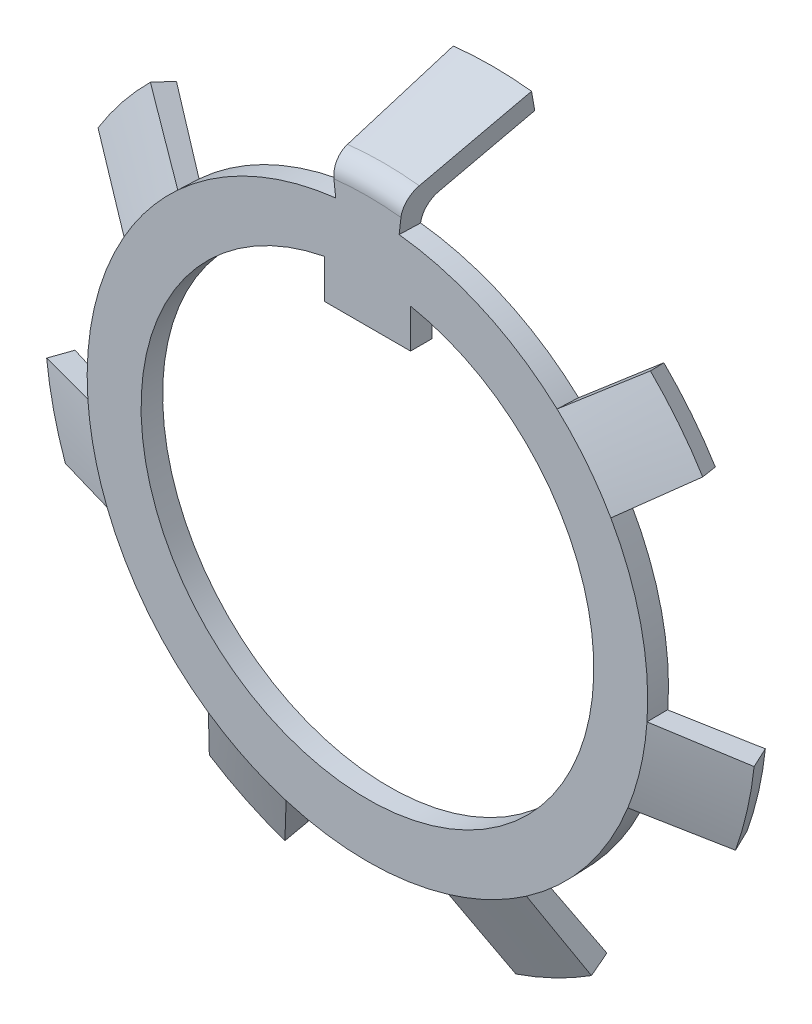
SolidWorks part; units mm, degrees
ref_plane "Front Plane" through (0, 0, 0) normal (0, 0, 1) x (1, 0, 0)
ref_plane "Top Plane" through (0, 0, 0) normal (0, 1, 0) x (1, 0, 0)
ref_plane "Right Plane" through (0, 0, 0) normal (1, 0, 0) x (0, 0, -1)
sketch "Sketch1" plane through (0, 0, 0) normal (1, 0, 0) x (0, 0, -1)
  line L0 (-1, 0) -> (23.0727, 0) construction
  line L1 (-1, 7.5) -> (-1, 13)
  line L2 (-1, 13) -> (0.529, 16.5)
  line L3 (0.529, 16.5) -> (1.4454, 16.0997)
  line L4 (1.4454, 16.0997) -> (0, 13)
  line L5 (0, 13) -> (0, 7.5)
  line L6 (0, 7.5) -> (-1, 7.5)
  dimension "D1" = 15
  dimension "D2" = 1
  dimension "D3" = 25
  dimension "D4" = 33
  dimension "D5" = 26
revolve "Revolve1" add sketch "Sketch1" angle 360 about L0
sketch "Sketch2" plane through (0, 0, 0) normal (0, 0, 1) x (1, 0, 0)
  line L0 (-2, 8.5) -> (-2, 10.3078)
  line L1 (-2, 8.5) -> (2, 8.5)
  line L5 (2, 8.5) -> (2, 10.3078)
  arc A0 (-2, 10.3078) -> (2, 10.3078) centre (0, 0) ccw
  point P1 (0, 8.5)
  dimension "D2" = 4
  dimension "D3" = 10.5
  dimension "D1" = 8.5
extrude "Cut-Extrude2" cut sketch "Sketch2" against normal through all both and the other way through all
sketch "Sketch3" plane through (0, 0, 1) normal (0, 0, 1) x (1, 0, 0)
  line L0 (0, 16.5) -> (0, 13) construction
  line L1 (14.0521, 8.6481) -> (11.2898, 6.4452)
  line L2 (2, 16.3783) -> (2, 12.8452)
  line L3 (-2, 16.3783) -> (-2, 12.8452)
  line L6 (11.5581, 11.7754) -> (8.7958, 9.5725)
  line L7 (15.5227, -5.5944) -> (12.0781, -4.8082)
  line L8 (16.4127, -1.6947) -> (12.9682, -0.9085)
  line L9 (5.3044, -15.6241) -> (3.7714, -12.4409)
  line L10 (8.9082, -13.8886) -> (7.3753, -10.7054)
  line L11 (-8.9082, -13.8886) -> (-7.3753, -10.7054)
  line L12 (-5.3044, -15.6241) -> (-3.7714, -12.4409)
  line L13 (-16.4127, -1.6947) -> (-12.9682, -0.9085)
  line L14 (-15.5227, -5.5944) -> (-12.0781, -4.8082)
  line L15 (-11.5581, 11.7754) -> (-8.7958, 9.5725)
  line L16 (-14.0521, 8.6481) -> (-11.2898, 6.4452)
  circle A0 centre (0, 0) radius 16.5 construction
  circle A1 centre (0, 0) radius 16.5
  circle A2 centre (0, 0) radius 13
  circle A3 centre (0, 0) radius 13 construction
  circle A4 centre (0, 0) radius 13
  circle A5 centre (0, 0) radius 13
  circle A6 centre (0, 0) radius 13
  circle A7 centre (0, 0) radius 13
  circle A8 centre (0, 0) radius 13
  circle A9 centre (0, 0) radius 13
  circle A10 centre (0, 0) radius 13 construction
  point P39 (0, 0)
  circle M12 centre (0, 0) radius 13
  dimension "D2" = 4
  dimension "D1" = 7
extrude "Cut-Extrude4" cut sketch "Sketch3" against normal blind 10 draft 2 contours A2 A1 L2 | A1 L0 A2 L2 | L0 A1 L3 A2 | A2 L3 A1 | A2 A1 | A2 A1 | A2 A1 | L8 A1 L1 M12 | L16 A1 L13 M12 region at (1.0016, 14.7039, 1) region at (-1.0016, 14.7039, 1) region at (6.3377, 13.1604, 1) region at (-6.3377, 13.1604, 1) region at (14.2407, 3.2503, 1) region at (-14.2407, 3.2503, 1) region at (-11.4202, -9.1073, 1) region at (11.4202, -9.1073, 1) region at (0, -14.6069, 1) draft outward yes
sketch "Sketch4" plane through (0, 0, 0) normal (1, 0, 0) x (0, 0, -1)
  line L0 (-1, 0) -> (23.0727, 0) construction
  line L1 (-1, 10) -> (-1, 14.5)
  line L2 (-1, 14.5) -> (4.7956, 16.0529)
  line L3 (4.7956, 16.0529) -> (5.0544, 15.087)
  line L4 (5.0544, 15.087) -> (0, 13.7327)
  line L5 (0, 13.7327) -> (0, 10)
  line L6 (0, 10) -> (-1, 10)
  dimension "D1" = 20
  dimension "D2" = 1
  dimension "D3" = 75
  dimension "D4" = 6
  dimension "D5" = 29
revolve "Revolve3" add sketch "Sketch4" angle 13 mid plane about L0
fillet "Fillet1" radius 1 2 edges at (0, 14.5, 1) (0, 13.7327, 0)
equation "\"d_ext_rouleau\"= 90"
equation "\"epaisseur_rouleau\"=80"
equation "\"alesage-rouleau\"= 52"
equation "\"jeu_dent_rouleau\"= 2"
equation "\"profondeur_dent_rouleau\"=4"
equation "\"n_dent_roueau\"= 15"
equation "\"d_ext_roulement_rouleau\"= 42"
equation "\"d_int_roulement_rouleau\"= 20"
equation "\"B_roulement_rouleau\"= 12"
equation "\"r_roulement_rouleau\"= 0.6"
equation "\"d_bille_roulement_rouleau\"= 8"
equation "\"F_anneau_alesage_rouleau\"=1.85"
equation "\"G_anneau_alesage_rouleau\"=47.5"
equation "\"K_anneau_alesage_rouleau\"=3.75"
equation "\"d_vis_flasque_rouleau\"=5"
equation "\"l-x_vis_flasque_rouleau\"=4"
equation "\"g_anneau_arbre_rouleau\"=19"
equation "\"f_anneau_arbre_rouleau\"=1.3"
equation "\"k_anneau_arbre_rouleau\"=1.5"
equation "\"entrax_vis_rouleau\"=65"
equation "\"d_granulat\"= 8"
equation "\"h_matrice\"= 18"
equation "\"d_matrice\"= 220"
equation "\"zone_vide_matrice\" = 48"
equation "\"d_alesage_matrice\"=20"
equation "\"a_clavette_alesage_matrice\"=6"
equation "\"B_roulement_matrice\"= 12"
equation "\"d_ext_roulement_matrice\"= 42"
equation "\"d_int_roulement_matrice\"= 20"
equation "\"r_roulement_matrice\"= 1"
equation "\"h_epaulement_arbre_matrice\" = 100"
equation "\"h_polie_matrice\" = 40"
equation "\"l_arbre_matrice\" = 300"
equation "\"d_int_ecrou_encouch_matrice\" = 20"
equation "\"d_ext_ecrou_encouch_matrice\" = 32"
equation "\"b_ecrou_encouch_matrice\" = 6"
equation "\"s_ecrou_encouch_matrice\" = 4"
equation "\"G_ecrou_encouch_matrice\" = 1"
equation "\"D2@Sketch1\"=\"G_ecrou_encouch_matrice\""
equation "\"D2@Sketch3\"=\"s_ecrou_encouch_matrice\""
equation "\"E_ecrou_encouch_matrice\" = 4"
equation "\"D2@Sketch2\"=\"E_ecrou_encouch_matrice\""
